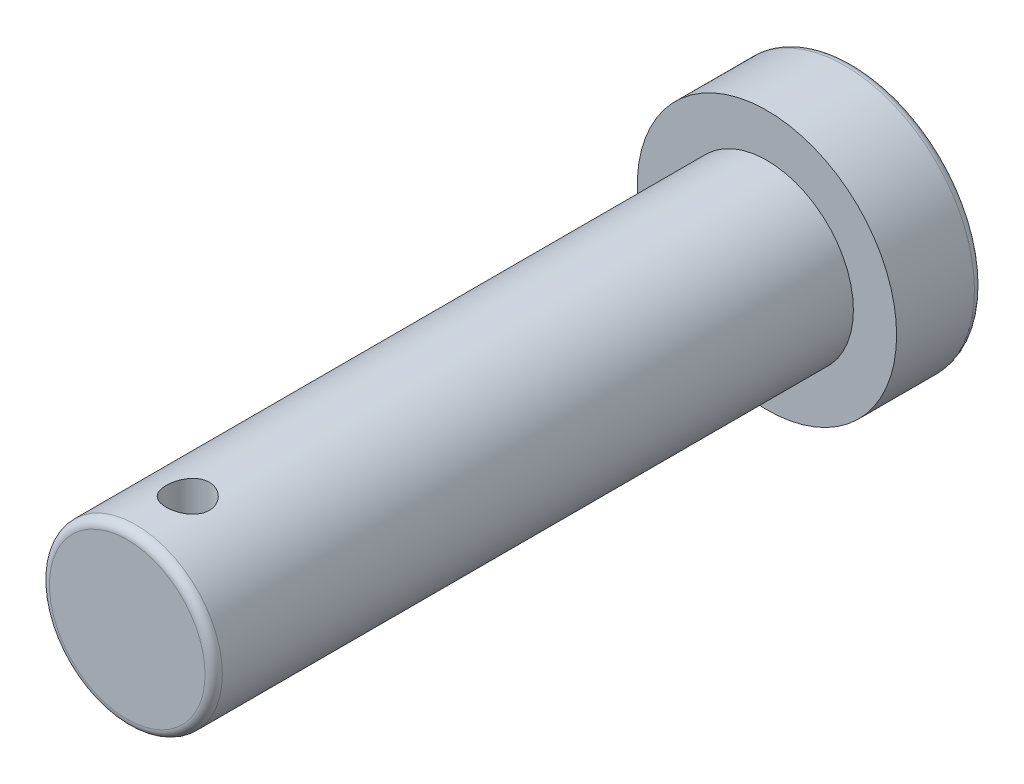
SolidWorks part; units mm, degrees
ref_plane "Front Plane" through (0, 0, 0) normal (0, 0, 1) x (1, 0, 0)
ref_plane "Top Plane" through (0, 0, 0) normal (0, 1, 0) x (1, 0, 0)
ref_plane "Right Plane" through (0, 0, 0) normal (1, 0, 0) x (0, 0, -1)
sketch "Sketch1" plane through (0, 0, 0) normal (0, 0, 1) x (1, 0, 0)
  circle A1 centre (0, 0) radius 15
extrude "Boss-Extrude1" add sketch "Sketch1" along normal blind 10
sketch "Sketch2" plane through (0, 0, 10) normal (0, 0, 1) x (1, 0, 0)
  circle A0 centre (0, 0) radius 10
extrude "Boss-Extrude2" add sketch "Sketch2" along normal blind 74
sketch "Sketch3" plane through (0, 0, 0) normal (0, 1, 0) x (1, 0, 0)
  circle A0 centre (0, -77) radius 2.5
  point P6 (0, -77)
extrude "Cut-Extrude1" cut sketch "Sketch3" against normal blind 74 and the other way blind 74
fillet "Fillet1" radius 1 1 edges at (15, 0, 0)
fillet "Fillet2" radius 1 1 edges at (10, 0, 84)
